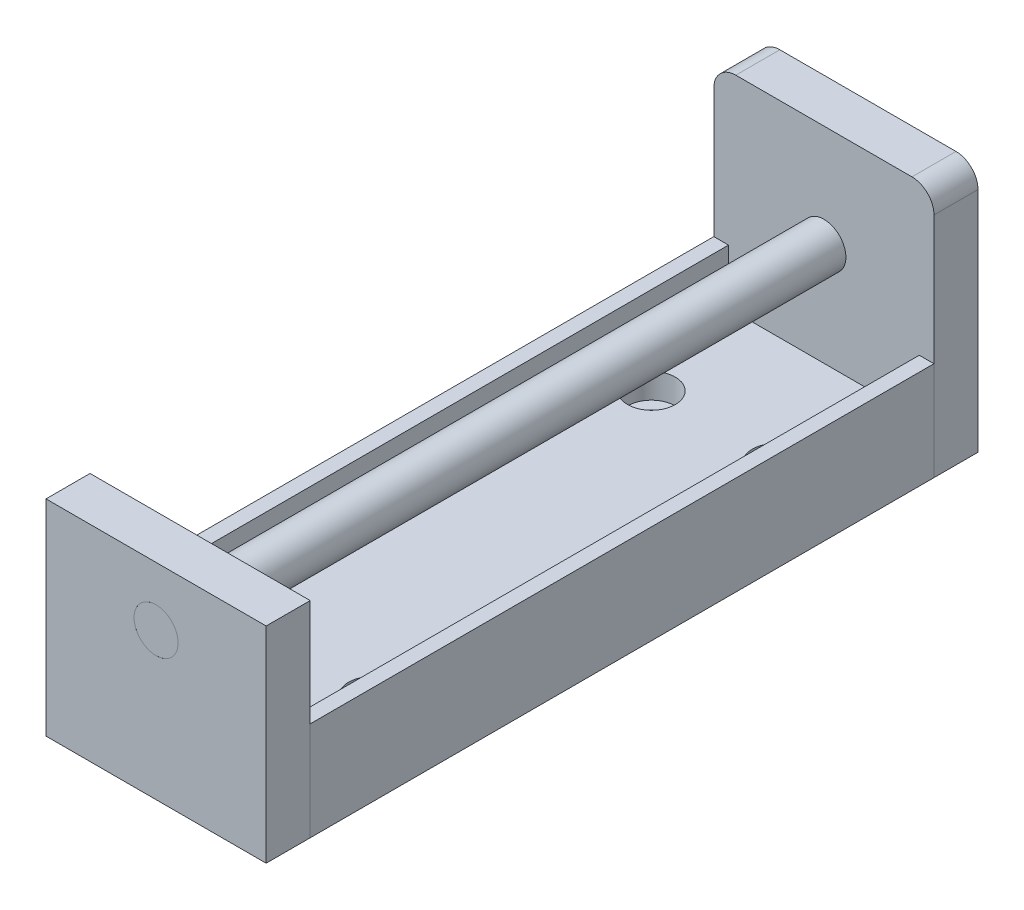
SolidWorks part; units mm, degrees
note: The reader was unsure of these and kept them because the rebuilt part matched: shared geometry of "Sketch4<2>".
ref_plane "Front Plane" through (0, 0, 0) normal (0, 0, 1) x (1, 0, 0)
ref_plane "Top Plane" through (0, 0, 0) normal (0, 1, 0) x (1, 0, 0)
ref_plane "Right Plane" through (0, 0, 0) normal (1, 0, 0) x (0, 0, -1)
sketch "Sketch1" plane through (0, 0, 15) normal (0, 0, 1) x (1, 0, 0)
  line L0 (11, 14) -> (-11, 14) construction
  line L1 (-15, 14) -> (15, 14)
  line L2 (-15, 14) -> (-15, -20)
  line L3 (-15, -20) -> (15, -20)
  line L4 (15, 14) -> (15, -20)
  point P4 (0, 14)
  dimension "D1" = 30
  dimension "D2" = 34
extrude "Boss-Extrude1" add sketch "Sketch1" along normal blind 6
sketch "Sketch2" plane through (0, 0, 21) normal (0, 0, 1) x (1, 0, 0)
  line L0 (-15, -6.55) -> (-13, -6.55)
  line L1 (-15, 14) -> (-15, -20) construction
  line L2 (-13, -6.55) -> (-13, -14)
  line L3 (-13, -14) -> (13, -14)
  line L4 (13, -14) -> (13, -6.55)
  line L5 (13, -6.55) -> (15, -6.55)
  line L6 (15, -20) -> (15, 14) construction
  line L7 (15, -6.55) -> (15, -20)
  line L8 (15, -20) -> (-15, -20)
  line L9 (-15, -20) -> (-15, -6.55)
  dimension "D1" = 2
  dimension "D2" = 2
  dimension "D3" = 6
  dimension "D4" = 13.45
extrude "Boss-Extrude2" add sketch "Sketch2" along normal blind 85 separate body
sketch "Sketch3" plane through (0, 0, 106) normal (0, 0, 1) x (1, 0, 0)
  line L1 (-15, -20) -> (15, -20)
  line L2 (-15, -20) -> (-15, 8)
  line L3 (-15, 8) -> (15, 8)
  line L4 (15, -20) -> (15, 8)
  dimension "D1" = 28
extrude "Boss-Extrude3" add sketch "Sketch3" along normal blind 6 separate body
fillet "Fillet1" radius 3 2 edges at (15, 14, 18) (-15, 14, 18)
sketch "Sketch4" plane through (0, 0, 21) normal (0, 0, 1) x (1, 0, 0)
  circle A0 centre (0, 0) radius 3
  dimension "D1" = 6
extrude "Cut-Extrude1" cut sketch "Sketch4" against normal through all both and the other way through all
extrude "Boss-Extrude4" add sketch "Sketch4<2>" against normal up to surface and the other way up to surface separate body contours A0
sketch "Sketch4<2>" plane through (0, 0, 21) normal (0, 0, 1) x (1, 0, 0) same geometry as "Sketch4"
sketch "Sketch5" plane through (0, -14, 0) normal (0, 1, 0) x (1, 0, 0)
  line L0 (0, 0) -> (0, -36) construction
  line L1 (-8.5, -36) -> (8.5, -36) construction
  line L2 (-8.5, -36) -> (-8.5, -91) construction
  line L3 (-8.5, -91) -> (8.5, -91) construction
  line L4 (8.5, -36) -> (8.5, -91) construction
  line L5 (13, -21) -> (-13, -21) construction
  line L6 (13, -106) -> (-13, -106) construction
  dimension "D1" = 17
  dimension "D2" = 15
  dimension "D3" = 15
hole_wizard "CBORE for M3 Hex Socket Head Cap Screw1" positions "Sketch6" profile "Sketch7" counterbore size "M3" standard "ISO" end condition through all
sketch "Sketch6" plane through (0, -14, 0) normal (0, 1, 0) x (1, 0, 0)
  point P0 (-8.5, -36)
  point P3 (8.5, -36)
  point P6 (8.5, -91)
  point P9 (-8.5, -91)
sketch "Sketch7" plane through (-8.5, -14, 36) normal (1, 0, 0) x (0, 0, 1)
  line L0 (0, 0) -> (0, 6)
  line L1 (0, 6) -> (1.6, 6)
  line L3 (1.6, 6) -> (1.6, 3.4)
  line L4 (1.6, 3.4) -> (3.25, 3.4)
  line L5 (3.25, 3.4) -> (3.25, 0)
  line L7 (3.25, 0) -> (0, 0)
  line L11 (0, -6.35) -> (0, 107.95) construction
  dimension "Thru Hole Dia." = 3.2
  dimension "Thru Hole Depth" = 6
  dimension "C'Bore Dia." = 6.5
  dimension "C'Bore Depth" = 3.4
equation "\"D2@Sketch2\"=\"D1@Sketch2\""
equation "\"D3@Sketch5\"=\"D2@Sketch5\""
